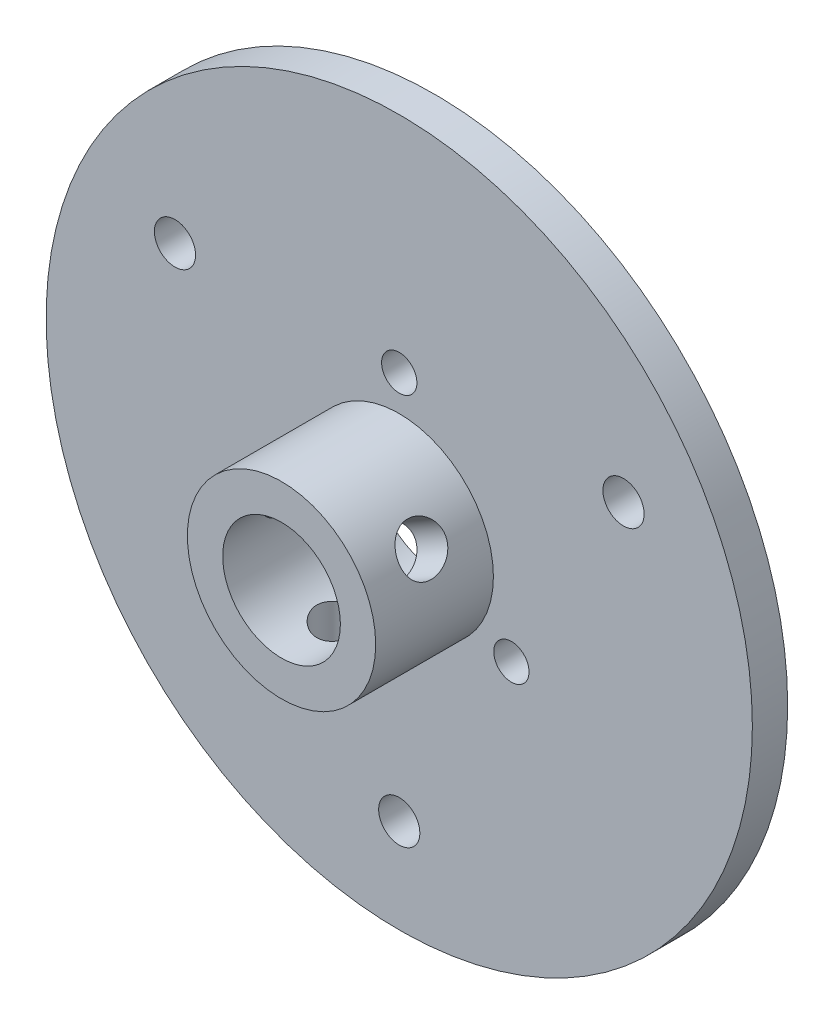
SolidWorks part; units mm, degrees
ref_plane "Front Plane" through (0, 0, 0) normal (0, 0, 1) x (1, 0, 0)
ref_plane "Top Plane" through (0, 0, 0) normal (0, 1, 0) x (1, 0, 0)
ref_plane "Right Plane" through (0, 0, 0) normal (1, 0, 0) x (0, 0, -1)
sketch "Sketch2" plane through (0, 0, 0) normal (0, 0, 1) x (1, 0, 0)
  circle A0 centre (0, 0) radius 5
  circle A2 centre (0, 0) radius 22 construction
  circle A3 centre (0, 0) radius 30
  circle A4 centre (0, -22) radius 1.75
  circle A5 centre (-19.0526, 11) radius 1.75
  circle A6 centre (19.0526, 11) radius 1.75
  point P7 (14.7567, 5.4969)
  point P8 (0, 0)
  point P13 (0, 0)
  dimension "D1" = 3
  dimension "D2" = 44
  dimension "D3" = 3.5
  dimension "D4" = 10
  dimension "D5" = 60
extrude "Boss-Extrude1" add sketch "Sketch2" along normal blind 3
sketch "Sketch3" plane through (0, 0, 3) normal (0, 0, 1) x (1, 0, 0)
  circle A0 centre (0, 0) radius 8
  circle A1 centre (0, 0) radius 5
  dimension "D1" = 16
extrude "Boss-Extrude2" add sketch "Sketch3" along normal blind 10
sketch "Sketch4" plane through (0, 0, 3) normal (0, 0, 1) x (1, 0, 0)
  circle A10 centre (0, 11) radius 1.5
  circle A11 centre (9.5263, -5.5) radius 1.5
  circle A12 centre (-9.5263, -5.5) radius 1.5
  point P0 (0, 12.6616)
  point P11 (0, 0)
  point P12 (0, 0)
  point P13 (0, 0)
  dimension "D1" = 3
  dimension "D2" = 3
  dimension "D3" = 11
extrude "Cut-Extrude2" cut sketch "Sketch4" against normal through all contours A12 | A11 | A10
sketch "Sketch12" plane through (0, 0, 0) normal (0, 1, 0) x (1, 0, 0)
  circle A0 centre (0, -8) radius 2
  point P2 (0, -10.0965)
  point P3 (0, -7.5169)
  dimension "D1" = 4
  dimension "D2" = 8
extrude "Cut-Extrude3" cut sketch "Sketch12" against normal blind 11.4938
pattern_circular "CirPattern1" count 3 every 120 about axis through (0, 0, 13) along (0, 0, 1) of "Cut-Extrude3"
